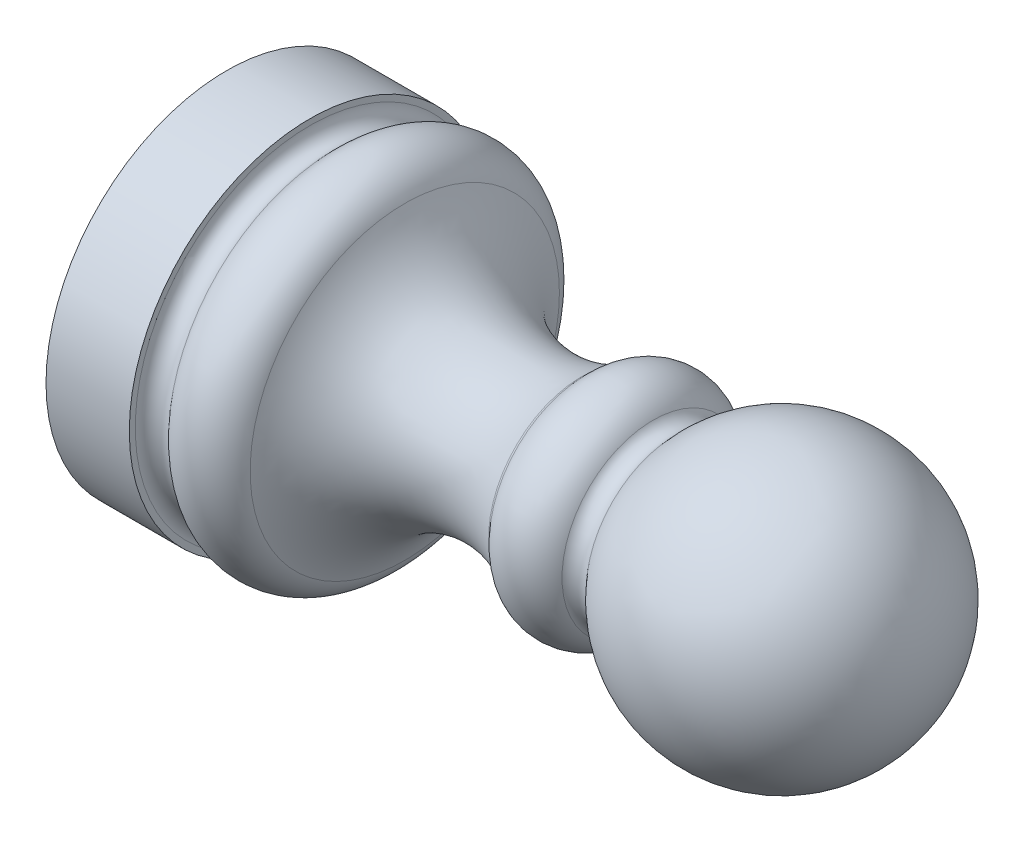
SolidWorks part; units mm, degrees
material "6061-T6 (SS)"
ref_plane "Front" through (0, 0, 0) normal (0, 0, 1) x (1, 0, 0)
ref_plane "Top" through (0, 0, 0) normal (0, 1, 0) x (1, 0, 0)
ref_plane "Right" through (0, 0, 0) normal (1, 0, 0) x (0, 0, -1)
sketch "Sketch1" plane through (0, 0, 0) normal (0, 0, 1) x (1, 0, 0)
  line L0 (0, 0) -> (0, -6.5)
  line L1 (0, -6.5) -> (3, -6.5)
  line L2 (0, 0) -> (-8.1317, 0) construction
  line L3 (0, 0) -> (25, 0)
  line L4 (3, -6.5) -> (3, -6.2856)
  line L6 (3.883, -5.9642) -> (1.6828, -3.3421) construction
  line L7 (16.1698, -3.2139) -> (14.4576, -1.1734) construction
  line L8 (12.9265, -3.4642) -> (11.3926, -1.6361) construction
  arc A0 (3, -6.2856) -> (3.883, -5.9642) centre (3.5, -6.2856) cw
  arc A1 (3.883, -5.9642) -> (6.4203, -5.5683) centre (5.0321, -5) ccw
  arc A2 (16.1698, -3.2139) -> (25, 0) centre (20, 0) ccw
  arc A3 (12.9265, -3.4642) -> (15.359, -3.2765) centre (14.0756, -2.5) ccw
  arc A5 (16.1698, -3.2139) -> (15.359, -3.2765) centre (15.7868, -3.5353) ccw
  arc A6 (6.4203, -5.5683) -> (12.7883, -3.3496) centre (10.5848, -7.2732) cw
  arc A7 (12.7883, -3.3496) -> (12.9265, -3.4642) centre (12.5435, -3.7856) cw
  dimension "D2" = 10
  dimension "D6" = 0.2144
  dimension "D7" = 1.5
  dimension "D4" = 0.5
  dimension "D8" = 40
  dimension "D10" = 1.5
  dimension "D11" = 4.5
  dimension "D9" = 8
  dimension "D1" = 13
  dimension "D3" = 25
  dimension "D5" = 3
revolve "Revolve1" add sketch "Sketch1" angle 360 about L2
sketch "Sketch3" [suppressed] plane through (0, 0, 0) normal (1, 0, 0) x (0, 0, -1)
  line L0 (6.2765, 13.6237) -> (0, 10)
  line L1 (0, 10) -> (-6.2765, 13.6237)
  line L2 (0, 0) -> (0, 11.2986) construction
  line L3 (0, 0) -> (12.9904, 7.5) construction
  line L4 (0, 0) -> (-12.9904, 7.5) construction
  line L5 (12.7332, 7.9288) -> (0, 0.5774)
  line L6 (0, 0.5774) -> (-12.7332, 7.9288)
  circle A0 centre (0, 0) radius 10 construction
  arc A1 (-6.2765, 13.6237) -> (-12.7332, 7.9288) centre (0, 0) ccw
  arc A2 (12.7332, 7.9288) -> (6.2765, 13.6237) centre (0, 0) ccw
  dimension "D2" = 20
  dimension "D5" = 30
  dimension "D1" = 120
  dimension "D3" = 120
  dimension "D4" = 1
extrude "Boss-Extrude1" [suppressed] add sketch "Sketch3" along normal blind 18 from offset 2 separate body
combine bodies "Combine1" [suppressed] operation type add bodies to combine 109 108
other "Move Face1" [suppressed] flip direction yes offset 0.005 parameters "D1"=0.005
pattern_circular "CirPattern1" [suppressed] count 3 over 360 of bodies 112
